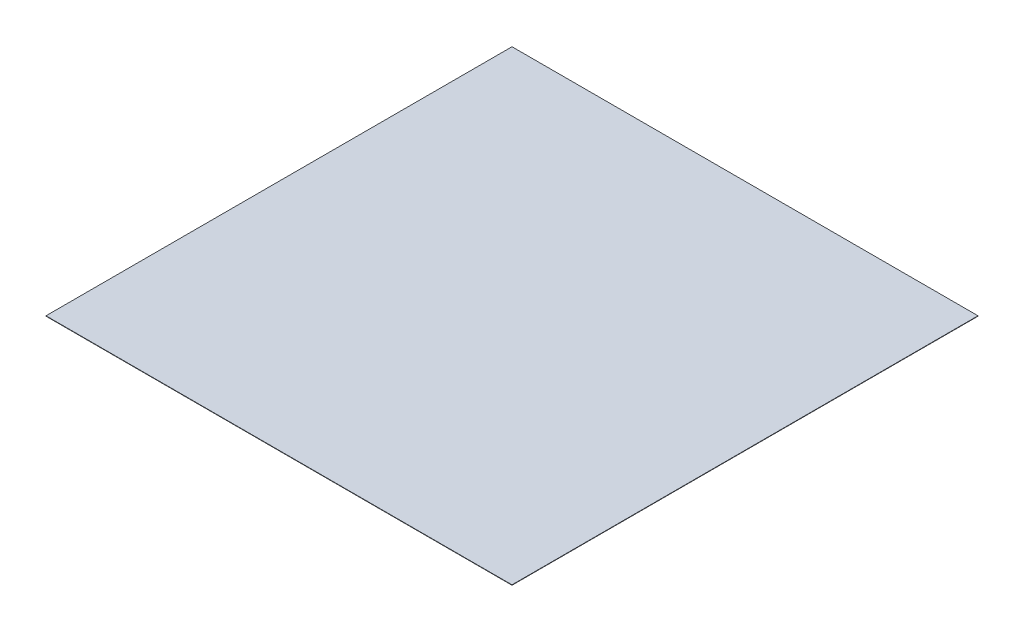
SolidWorks part; units mm, degrees
ref_plane "Front Plane" through (0, 0, 0) normal (0, 0, 1) x (1, 0, 0)
ref_plane "Top Plane" through (0, 0, 0) normal (0, 1, 0) x (1, 0, 0)
ref_plane "Right Plane" through (0, 0, 0) normal (1, 0, 0) x (0, 0, -1)
sketch "Sketch1" plane through (0, 0, 0) normal (0, 1, 0) x (1, 0, 0)
  line L1 (-1524, 1524) -> (1524, 1524)
  line L2 (-1524, 1524) -> (-1524, -1524)
  line L3 (-1524, -1524) -> (1524, -1524)
  line L4 (1524, 1524) -> (1524, -1524)
  line L5 (-1524, 1524) -> (1524, -1524) construction
  line L6 (-1524, -1524) -> (1524, 1524) construction
  point P0 (0, 0)
  dimension "D1" = 3048
  dimension "D2" = 3048
extrude "Boss-Extrude1" add sketch "Sketch1" along normal blind 2.54
